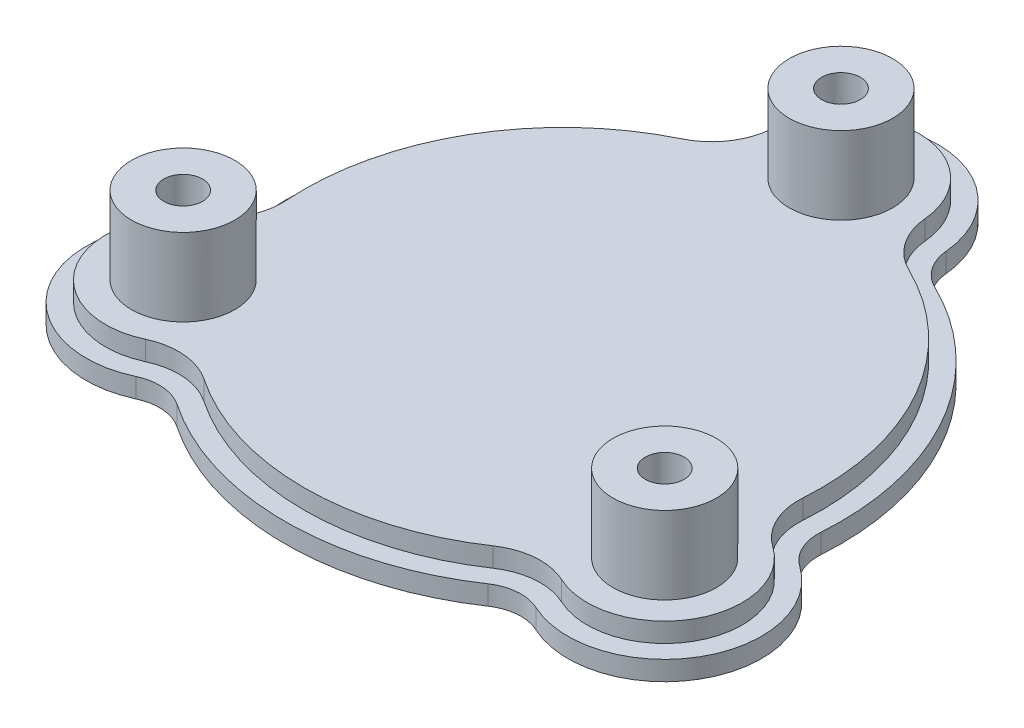
SolidWorks part; units mm, degrees
ref_plane "Front Plane" through (0, 0, 0) normal (0, 0, 1) x (1, 0, 0)
ref_plane "Top Plane" through (0, 0, 0) normal (0, 1, 0) x (1, 0, 0)
ref_plane "Right Plane" through (0, 0, 0) normal (1, 0, 0) x (0, 0, -1)
sketch "Sketch2" plane through (0, 0, 0) normal (0, 1, 0) x (1, 0, 0)
  line L0 (0, 49.4745) -> (0, 0) construction
  circle A0 centre (0, 0) radius 43 construction
  circle A1 centre (0, 43) radius 3
  circle A3 centre (0, 43) radius 8
  circle A4 centre (37.2391, -21.5) radius 3
  circle A6 centre (37.2391, -21.5) radius 8
  circle A7 centre (-37.2391, -21.5) radius 3
  circle A9 centre (-37.2391, -21.5) radius 8
  point P19 (0, 0)
  dimension "D1" = 86
  dimension "D2" = 6
  dimension "D3" = 3
extrude "Boss-Extrude2" add sketch "Sketch2" against normal blind 6
sketch "Sketch3" plane through (0, -6, 0) normal (0, -1, 0) x (1, 0, 0)
  line L0 (0, 0) -> (0, -87.18) construction
  arc A0 (-14.9415, -44.324) -> (14.9415, -44.324) centre (0, -43) ccw
  arc A1 (18.8462, -38.65) -> (42.895, 3.0038) centre (0, 0) ccw
  arc A2 (18.8462, -38.65) -> (14.9415, -44.324) centre (21.9141, -44.9419) ccw
  arc A3 (-18.8462, -38.65) -> (-14.9415, -44.324) centre (-21.9141, -44.9419) cw
  circle A4 centre (0, -43) radius 6
  circle A5 centre (-37.2391, 21.5) radius 6
  arc A6 (-30.915, 35.1017) -> (-45.8564, 9.2223) centre (-37.2391, 21.5) ccw
  arc A7 (-42.895, 3.0038) -> (-45.8564, 9.2223) centre (-49.8779, 3.4927) ccw
  arc A8 (-24.0488, 35.6462) -> (-30.915, 35.1017) centre (-27.9637, 41.4491) cw
  circle A9 centre (37.2391, 21.5) radius 6
  arc A10 (45.8564, 9.2223) -> (30.915, 35.1017) centre (37.2391, 21.5) ccw
  arc A11 (24.0488, 35.6462) -> (30.915, 35.1017) centre (27.9637, 41.4491) ccw
  arc A12 (42.895, 3.0038) -> (45.8564, 9.2223) centre (49.8779, 3.4927) cw
  arc A13 (17.5313, -35.9535) -> (39.9023, 2.7942) centre (0, 0) ccw
  arc A14 (24.0488, 35.6462) -> (-24.0488, 35.6462) centre (0, 0) ccw
  arc A15 (39.9023, 2.7942) -> (44.133, 11.6779) centre (49.8779, 3.4927) cw
  arc A16 (-42.895, 3.0038) -> (-18.8462, -38.65) centre (0, 0) ccw
  arc A17 (44.133, 11.6779) -> (32.1798, 32.3813) centre (37.2391, 21.5) ccw
  arc A18 (22.371, 33.1593) -> (32.1798, 32.3813) centre (27.9637, 41.4491) ccw
  arc A19 (22.371, 33.1593) -> (-22.371, 33.1593) centre (0, 0) ccw
  arc A20 (-22.371, 33.1593) -> (-32.1798, 32.3813) centre (-27.9637, 41.4491) cw
  arc A21 (-32.1798, 32.3813) -> (-44.133, 11.6779) centre (-37.2391, 21.5) ccw
  arc A22 (-39.9023, 2.7942) -> (-44.133, 11.6779) centre (-49.8779, 3.4927) ccw
  arc A23 (-39.9023, 2.7942) -> (-17.5313, -35.9535) centre (0, 0) ccw
  arc A24 (-17.5313, -35.9535) -> (-11.9532, -44.0592) centre (-21.9141, -44.9419) cw
  arc A25 (-11.9532, -44.0592) -> (11.9532, -44.0592) centre (0, -43) ccw
  arc A26 (17.5313, -35.9535) -> (11.9532, -44.0592) centre (21.9141, -44.9419) ccw
  circle A28 centre (0, -43) radius 8
  circle A29 centre (-37.2391, 21.5) radius 8
  point P31 (0, 0)
  circle M2 centre (37.2391, 21.5) radius 8
  dimension "D1" = 7
  dimension "D2" = 86
  dimension "D3" = 30
  dimension "D4" = 3
  dimension "D5" = 3
extrude "Boss-Extrude3" add sketch "Sketch3" along normal blind 12 contours A4 A25 A26 A13 A15 A17 A18 A19 A20 A21 A22 A23 A24 A5 M2 | A13 A26 A25 A0 A2 A1 A12 A10 A11 A14 A8 A6 A7 A16 A3 A24 A23 A22 A21 A20 A19 A18 A17 A15 region at (-14.9506, -6, -40.1497) region at (0, -6, 0)
extrude "Cut-Extrude1" cut sketch "Sketch3<4>" along normal blind 6 contours A4 A25 A26 A13 A15 A17 A18 A19 A20 A21 A22 A23 A24 A5 M2 region at (0, -6, 0)
sketch "Sketch3<4>" plane through (0, -6, 0) normal (0, -1, 0) x (1, 0, 0) same geometry as "Sketch3"
extrude "Cut-Extrude3" cut sketch "Sketch3<6>" along normal blind 9 contours A13 A26 A25 A0 A2 A1 A12 A10 A11 A14 A8 A6 A7 A16 A3 A24 A23 A22 A21 A20 A19 A18 A17 A15 region at (-14.9506, -6, -40.1497)
sketch "Sketch3<6>" plane through (0, -6, 0) normal (0, -1, 0) x (1, 0, 0) same geometry as "Sketch3"
extrude "Boss-Extrude4" add sketch "Sketch3<8>" along normal blind 12 contours A9 M2 | A29 A5 | L0 A28 A4 | A28 L0 A4 region at (5.5304, -6, -37.4696) region at (-0.1789, -6, -36) region at (-45.0128, -6, 21.5) region at (29.4654, -6, 21.5)
sketch "Sketch3<8>" plane through (0, -6, 0) normal (0, -1, 0) x (1, 0, 0) same geometry as "Sketch3"
